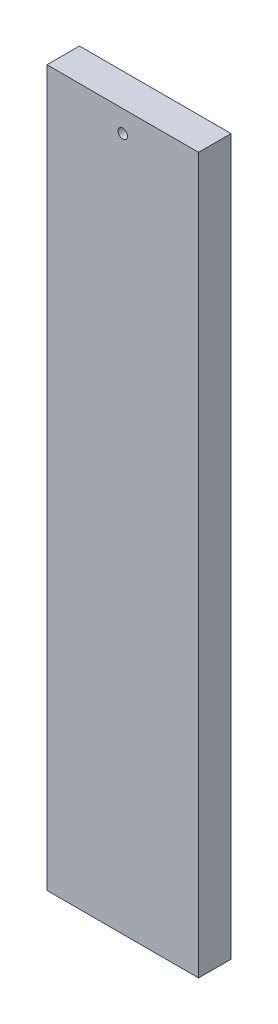
SolidWorks part; units mm, degrees
ref_plane "Front Plane" through (0, 0, 0) normal (0, 0, 1) x (1, 0, 0)
ref_plane "Top Plane" through (0, 0, 0) normal (0, 1, 0) x (1, 0, 0)
ref_plane "Right Plane" through (0, 0, 0) normal (1, 0, 0) x (0, 0, -1)
sketch "Sketch1" plane through (0, 0, 0) normal (0, 1, 0) x (1, 0, 0)
  line L1 (0, 0) -> (88.9, 0)
  line L2 (0, 0) -> (0, 19.05)
  line L3 (0, 19.05) -> (88.9, 19.05)
  line L4 (88.9, 0) -> (88.9, 19.05)
  dimension "D1" = 19.05
  dimension "D2" = 88.9
extrude "Boss-Extrude1" add sketch "Sketch1" along normal blind 419.1
sketch "Sketch2" plane through (0, 0, 0) normal (0, 0, 1) x (1, 0, 0)
  line L0 (44.45, 419.1) -> (44.45, 248.2649) construction
  line L1 (0, 419.1) -> (88.9, 419.1) construction
  circle A0 centre (44.45, 406.4) radius 2.7781
  dimension "D1" = 5.5562
  dimension "D2" = 12.7
extrude "Cut-Extrude1" cut sketch "Sketch2" against normal through all
